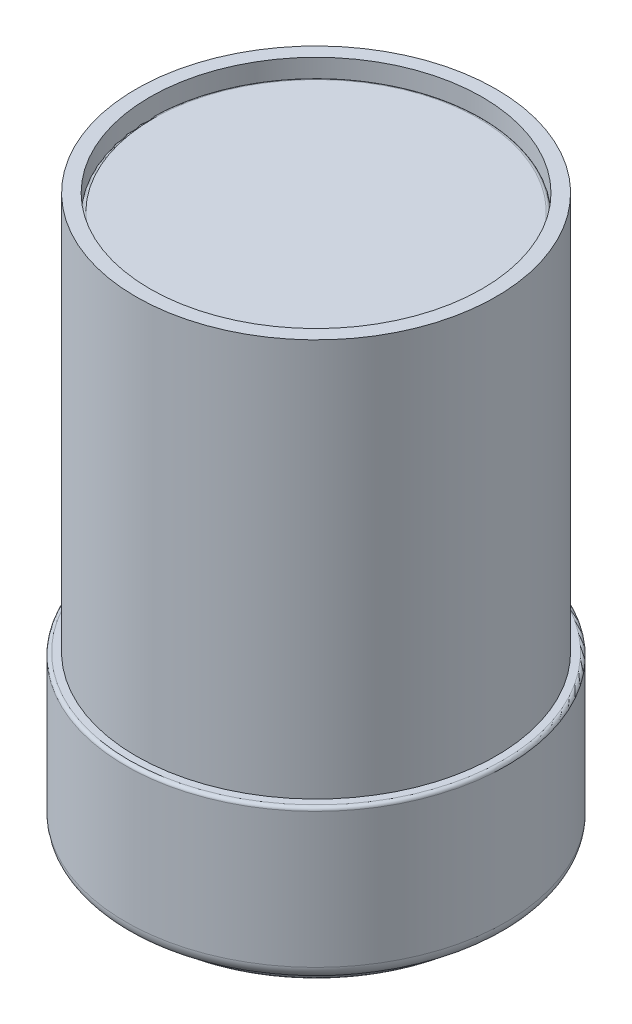
SolidWorks part; units mm, degrees
ref_plane "Front" through (0, 0, 0) normal (0, 0, 1) x (1, 0, 0)
ref_plane "Top" through (0, 0, 0) normal (0, 1, 0) x (1, 0, 0)
ref_plane "Right" through (0, 0, 0) normal (1, 0, 0) x (0, 0, -1)
sketch "Sketch1" plane through (0, 0, 0) normal (0, 1, 0) x (1, 0, 0)
  circle A0 centre (0, 0) radius 76.2
  dimension "D1" = 152.4
extrude "Boss-Extrude1" add sketch "Sketch1" along normal blind 169.7 and the other way blind 63.5
shell "Shell1" thickness 6.35 removed face at (0, 169.7, 76.2) outward yes
ref_plane "Plane1" through (0, -76.2, 0) normal (0, -1, 0) x (1, 0, 0)
sketch "Sketch2" plane through (0, -76.2, 0) normal (0, -1, 0) x (1, 0, 0)
  circle A0 centre (0, 0) radius 80.9625
  dimension "D1" = 161.925
extrude "Boss-Extrude2" add sketch "Sketch2" against normal blind 63.5 separate body
shell "Shell3" thickness 6.35 removed face at (0, -12.7, -80.9625) outward yes
fillet "Fillet1" radius 1.524 2 edges at (0, -12.7, -87.3125) (0, -12.7, -80.9625)
fillet "Fillet2" radius 6.35 1 edges at (0, -82.55, -87.3125)
sketch "Sketch3" plane through (0, -82.55, 0) normal (0, -1, 0) x (1, 0, 0)
  circle A0 centre (0, 0) radius 76.2
  circle A1 centre (0, 0) radius 69.85
  dimension "D1" = 6.35
  dimension "D2" = 152.4
extrude "Boss-Extrude3" add sketch "Sketch3" along normal blind 6.35
fillet "Fillet3" radius 6.35 1 edges at (0, -82.55, -76.2)
fillet "Fillet4" radius 1.524 2 edges at (0, -88.9, -69.85) (0, -88.9, -76.2)
sketch "Sketch4" plane through (0, -63.5, 0) normal (0, 1, 0) x (1, 0, 0)
  circle A0 centre (0, 0) radius 76.2
extrude "Boss-Extrude4" add sketch "Sketch4" along normal blind 225.425 separate body
fillet "Fillet5" radius 1.524 1 edges at (0, 161.925, 76.2)
